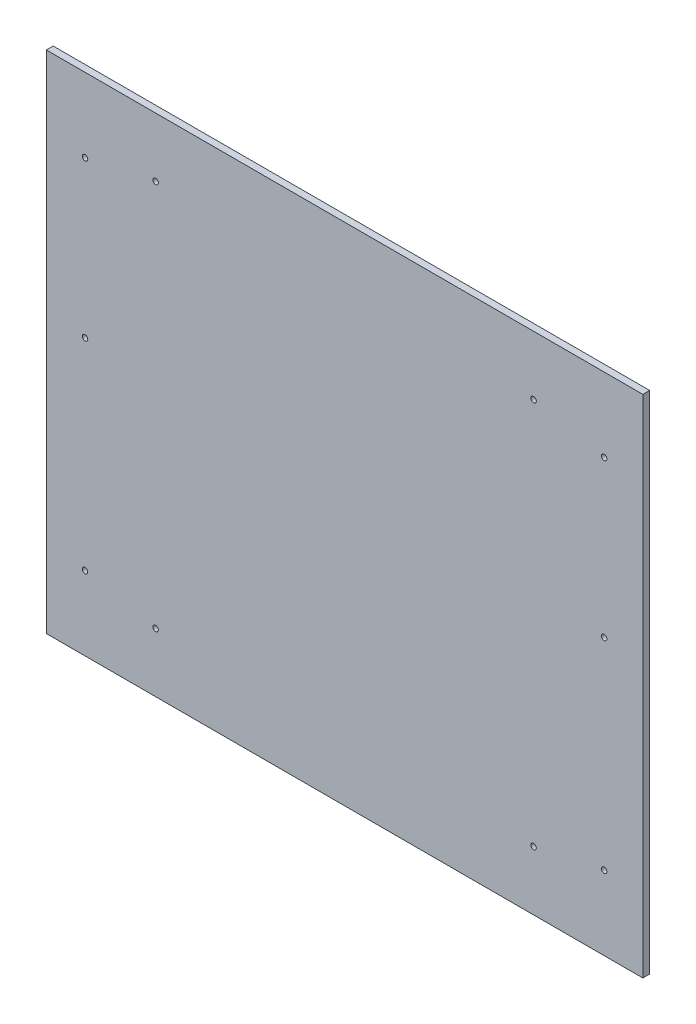
SolidWorks part; units mm, degrees
ref_plane "Front (1)" through (0, 0, 0) normal (0, 0, 1) x (1, 0, 0)
ref_plane "Top (2)" through (0, 0, 0) normal (0, 1, 0) x (1, 0, 0)
ref_plane "Right (3)" through (0, 0, 0) normal (1, 0, 0) x (0, 0, -1)
ref_axis "X-Axis" through (-80.9, 0, 0) along (1, 0, 0)
ref_axis "Y-Axis" through (0, -50, 0) along (0, 1, 0)
ref_axis "Z-Axis" through (0, 0, 50) along (0, 0, -1)
sketch "Sketch1" plane through (0, 0, 0) normal (0, 0, 1) x (1, 0, 0)
  line L1 (0, 0) -> (415.925, 0)
  line L2 (0, 0) -> (0, 352.425)
  line L3 (0, 352.425) -> (415.925, 352.425)
  line L4 (415.925, 0) -> (415.925, 352.425)
  dimension "D1" = 415.925
  dimension "D2" = 352.425
extrude "Boss-Extrude1" add sketch "Sketch1" along normal blind 4.7625
sketch "Sketch2" plane through (0, 0, 4.7625) normal (0, 0, 1) x (1, 0, 0)
  line L0 (0, 352.425) -> (0, 0) construction
  line L1 (415.925, 352.425) -> (0, 352.425) construction
  line L2 (207.9625, 352.425) -> (207.9625, 0) construction
  line L3 (0, 0) -> (415.925, 0) construction
  line L4 (415.925, 0) -> (415.925, 352.425) construction
  line L6 (415.925, 176.2125) -> (0, 176.2125) construction
  circle A0 centre (26.9875, 300.8376) radius 1.905
  circle A1 centre (76.2, 311.15) radius 1.905
  circle A2 centre (339.725, 311.15) radius 1.905
  circle A3 centre (388.9375, 300.8376) radius 1.905
  circle A4 centre (388.9375, 51.5874) radius 1.905
  circle A5 centre (339.725, 41.275) radius 1.905
  circle A6 centre (76.2, 41.275) radius 1.905
  circle A7 centre (26.9875, 51.5874) radius 1.905
  circle A8 centre (388.9375, 192.1129) radius 1.905
  circle A9 centre (26.9875, 192.1129) radius 1.905
  dimension "D6" = 176.2125
  dimension "D1" = 3.81
  dimension "D7" = 3.81
  dimension "D2" = 26.9875
  dimension "D3" = 76.2
  dimension "D4" = 51.5874
  dimension "D5" = 41.275
  dimension "D8" = 108.7247
extrude "Cut-Extrude1" cut sketch "Sketch2" against normal through all
sketch "Sketch3" plane through (0, 0, 0) normal (0, 0, -1) x (-1, 0, 0)
  line L0 (-415.925, 346.075) -> (-352.425, 346.075) construction
  line L1 (-415.925, 352.425) -> (0, 352.425) construction
  line L2 (-415.925, 0) -> (-415.925, 352.425) construction
  text T0 "LCSAP-607"
  dimension "D1" = 63.5
  dimension "D2" = 6.35
extrude "Cut-Extrude2" cut sketch "Sketch3" against normal blind 1.016
